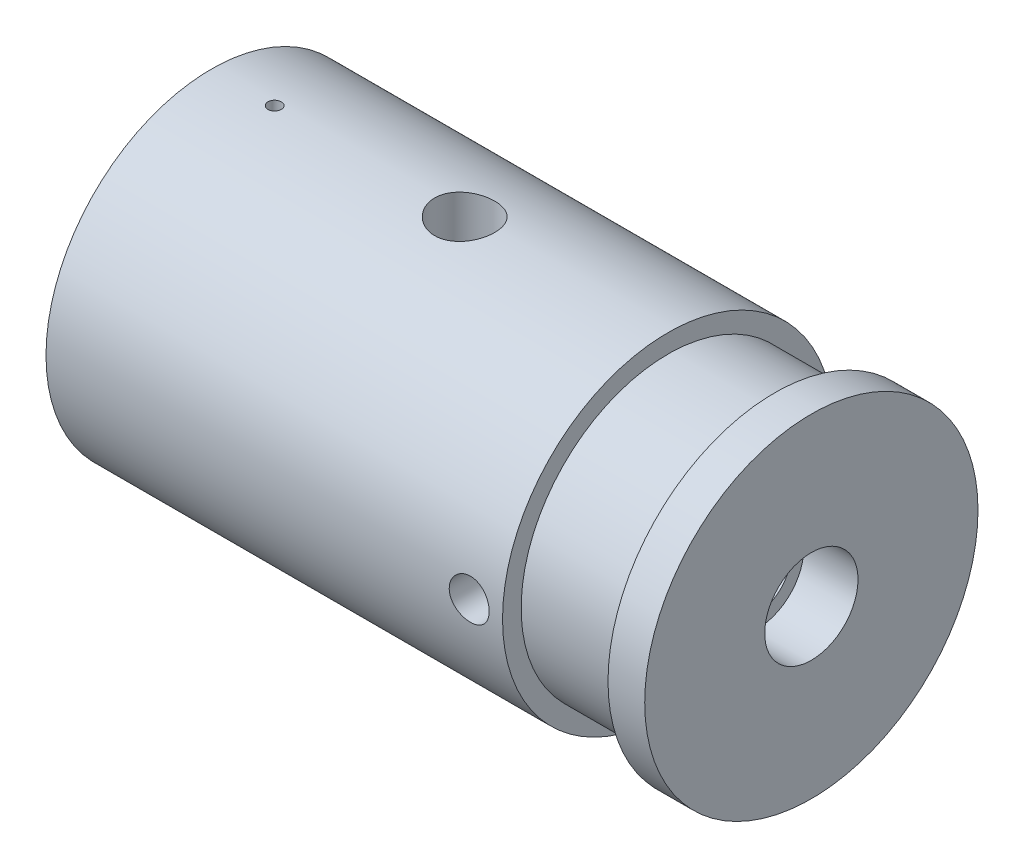
SolidWorks part; units mm, degrees
material "AISI 316 Stainless Steel Sheet (SS)"
ref_plane "Front Plane" through (0, 0, 0) normal (0, 0, 1) x (1, 0, 0)
ref_plane "Top Plane" through (0, 0, 0) normal (0, 1, 0) x (1, 0, 0)
ref_plane "Right Plane" through (0, 0, 0) normal (1, 0, 0) x (0, 0, -1)
sketch "Sketch1" plane through (0, 0, 0) normal (0, 0, 1) x (1, 0, 0)
  line L0 (0, 0) -> (0, 24.8206)
  line L1 (0, 24.8206) -> (68.4895, 24.8206)
  line L2 (68.4895, 24.8206) -> (68.4895, 22.0281)
  line L3 (68.4895, 22.0281) -> (84.492, 22.0281)
  line L4 (84.492, 22.0281) -> (84.492, 25)
  line L5 (84.492, 25) -> (90, 25)
  line L6 (90, 25) -> (90, 0)
  line L7 (90, 0) -> (0, 0)
  line L8 (0, 0) -> (-9.0426, 0) construction
  line L9 (-9.0426, 0) -> (117.8661, 0) construction
  point P9 (0, 0)
  point P12 (0, 0)
  dimension "D1" = 25
  dimension "D2" = 90
revolve "Revolve1" add sketch "Sketch1" angle 360 about L8
sketch "Sketch3" plane through (0, 0, 0) normal (0, 1, 0) x (1, 0, 0)
  line L0 (0, 0) -> (0, 13)
  line L1 (0, 24.8206) -> (0, -24.8206) construction
  line L2 (0, 13) -> (11.1868, 13)
  line L3 (11.1868, 13) -> (11.1868, 11)
  line L4 (11.1868, 11) -> (14.3932, 11)
  line L5 (14.3932, 11) -> (14.3932, 9)
  line L6 (14.3932, 9) -> (69.9226, 9)
  line L7 (69.9226, 9) -> (69.9226, 5)
  line L8 (69.9226, 5) -> (81.8739, 5)
  line L9 (81.8739, 5) -> (81.8739, 7)
  line L10 (81.8739, 7) -> (90, 7)
  line L11 (90, -25) -> (90, 25) construction
  line L12 (90, 7) -> (90, 0)
  line L13 (90, 0) -> (0, 0)
  line L14 (0, 0) -> (96.4485, 0) construction
  line L15 (96.4485, 0) -> (-9.5092, 0) construction
  dimension "D1" = 7
  dimension "D2" = 5
  dimension "D3" = 11
  dimension "9" = 9
  dimension "D4" = 13
revolve "Cut-Revolve1" cut sketch "Sketch3" angle 360 about L15
ref_plane "Plane1" through (0, -25, 0) normal (0, 1, 0) x (1, 0, 0)
sketch "Sketch4" plane through (0, 0, 0) normal (0, 0, 1) x (1, 0, 0)
  line L0 (68.4895, 0) -> (38.044, 0) construction
  line L1 (68.4895, 0) -> (10.4895, 0) construction
  line L2 (68.4895, -22.0281) -> (68.4895, 22.0281) construction
  line L3 (90, 0) -> (0, 0) construction
  circle A0 centre (38.044, 0) radius 1.7
  dimension "D1" = 58
extrude "Cut-Extrude1" cut sketch "Sketch4" against normal blind 22 and the other way blind 21
sketch "Sketch5" plane through (0, 0, 0) normal (0, 0, 1) x (1, 0, 0)
  line L0 (68.4895, 0) -> (10.544, 0) construction
  line L1 (68.4895, -22.0281) -> (68.4895, 22.0281) construction
  line L2 (90, 0) -> (0, 0) construction
  circle A0 centre (10.544, 0) radius 1
extrude "Cut-Extrude2" cut sketch "Sketch5" against normal blind 32
ref_plane "Plane2" through (0, 25, 0) normal (0, 1, 0) x (1, 0, 0)
sketch "Sketch7" plane through (0, 25, 0) normal (0, 1, 0) x (1, 0, 0)
  line L0 (68.4895, 0) -> (37.9895, 0) construction
  line L1 (68.4895, -24.8206) -> (68.4895, 24.8206) construction
  circle A2 centre (37.9895, 0) radius 1.7
  dimension "D1" = 3.4
  dimension "30." = 30.5
extrude "Cut-Extrude3" cut sketch "Sketch7" against normal blind 61 and the other way through all
ref_plane "Plane3" through (0, 0, 25) normal (0, 0, 1) x (1, 0, 0)
sketch "Sketch8" plane through (0, 0, 25) normal (0, 0, 1) x (1, 0, 0)
  line L0 (68.4895, 0) -> (63.4895, 0) construction
  line L1 (68.4895, -22.0281) -> (68.4895, 22.0281) construction
  circle A2 centre (63.4895, 0) radius 1.7
  dimension "D2" = 3.4
  dimension "D1" = 5
extrude "Cut-Extrude4" cut sketch "Sketch8" against normal blind 25
sketch "Sketch9" plane through (0, 25, 0) normal (0, 1, 0) x (1, 0, 0)
  line L0 (68.4895, 0) -> (9.4895, 0)
  line L1 (68.4895, -22.0281) -> (68.4895, 22.0281) construction
  circle A0 centre (9.4895, 0) radius 1
  dimension "D2" = 2
  dimension "D1" = 59
extrude "Cut-Extrude5" cut sketch "Sketch9" against normal blind 25 contours A0
ref_axis "Axis1" through (0, 0, 0) along (1, 0, 0)
sketch "Sketch10" plane through (0, 25, 0) normal (0, 1, 0) x (1, 0, 0)
  circle A0 centre (37.9895, 0) radius 4.5
  dimension "D1" = 9
extrude "Cut-Extrude6" cut sketch "Sketch10" against normal blind 10
mirror "Mirror1" about plane through (0, 0, 0) normal (0, 1, 0) of "Cut-Extrude6"
sketch "Sketch11" plane through (0, 0, 25) normal (0, 0, 1) x (1, 0, 0)
  circle A0 centre (63.4895, 0) radius 3
extrude "Cut-Extrude7" cut sketch "Sketch11" against normal blind 13
